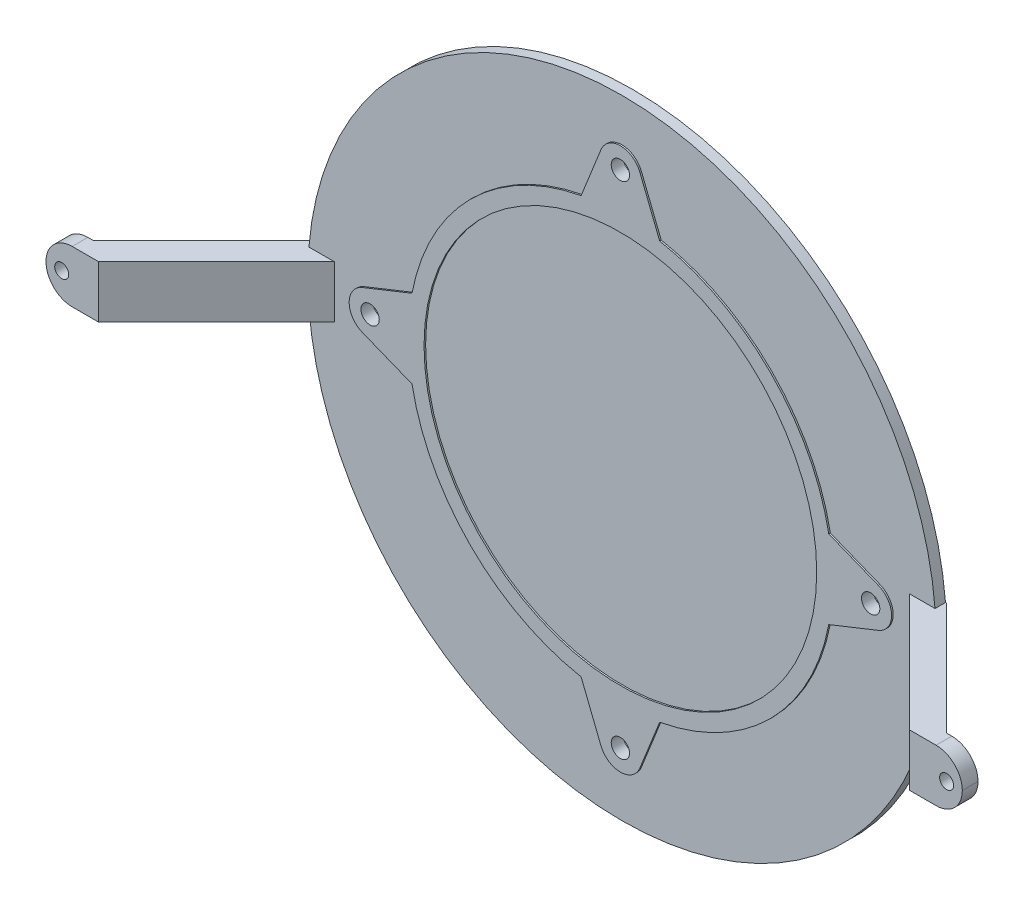
SolidWorks part; units mm, degrees
ref_plane "Front Plane" through (0, 0, 0) normal (0, 0, 1) x (1, 0, 0)
ref_plane "Top Plane" through (0, 0, 0) normal (0, 1, 0) x (1, 0, 0)
ref_plane "Right Plane" through (0, 0, 0) normal (1, 0, 0) x (0, 0, -1)
sketch "Sketch1" plane through (0, 0, 0) normal (0, 0, 1) x (1, 0, 0)
  circle A0 centre (0, 0) radius 60
  dimension "D1" = 120
extrude "Boss-Extrude1" add sketch "Sketch1" along normal blind 2
sketch "Sketch4" plane through (0, 0, 2) normal (0, 0, 1) x (1, 0, 0)
  circle A0 centre (0, 0) radius 37.5
  circle A1 centre (0, 0) radius 40.5
  dimension "D1" = 75
  dimension "D2" = 3
extrude "Boss-Extrude4" add sketch "Sketch4" along normal blind 0.3
sketch "Sketch5" plane through (0, 0, 2) normal (0, 0, 1) x (1, 0, 0)
  line L0 (-7.5, 39.7995) -> (7.5, 39.7995)
  line L1 (7.5, 39.7995) -> (3.715, 49.2823)
  line L2 (-7.5, 39.7995) -> (-3.715, 49.2823)
  line L3 (0, 39.7995) -> (0, 47.7995) construction
  arc A0 (3.715, 49.2823) -> (-3.715, 49.2823) centre (0, 47.7995) ccw
  circle A1 centre (0, 0) radius 40.5 construction
  circle A2 centre (0, 47.7995) radius 1.75
  dimension "D2" = 8
  dimension "D4" = 3.5
  dimension "D1" = 8
  dimension "D3" = 15
extrude "Boss-Extrude5" add sketch "Sketch5" along normal blind 0.3
pattern_circular "CirPattern1" count 4 over 360 about axis through (0, 0, 2) along (0, 0, -1) of "Boss-Extrude5"
sketch "Sketch6" plane through (0, 0, 2) normal (0, 0, 1) x (1, 0, 0)
  circle A1 centre (0, 47.7995) radius 1.75
  circle A2 centre (0, 47.7995) radius 1.75
  circle A3 centre (-47.7995, 0) radius 1.75
  circle A4 centre (-47.7995, 0) radius 1.75
  circle A5 centre (47.7995, 0) radius 1.75
  circle A6 centre (47.7995, 0) radius 1.75
  circle A7 centre (0, -47.7995) radius 1.75
  circle A8 centre (0, -47.7995) radius 1.75
  dimension "D1" = 0
  dimension "D2" = 0
  dimension "D3" = 0
  dimension "D4" = 0
extrude "Cut-Extrude1" cut sketch "Sketch6" against normal through all
sketch "Sketch7" plane through (0, 0, 0) normal (0, 1, 0) x (1, 0, 0)
  line L0 (60, 0) -> (81.5, -21.5)
  line L1 (87.5, -24.5) -> (77.4289, -24.5)
  line L2 (77.4289, -24.5) -> (52.9289, 0)
  line L3 (60, 0) -> (-60, 0) construction
  line L4 (52.9289, 0) -> (60, 0)
  line L6 (81.5, -21.5) -> (87.5, -21.5)
  line L7 (87.5, -21.5) -> (87.5, -24.5)
  point P8 (80.333, -24.4041)
  point P9 (81.3219, -23.5448)
  point P11 (79.0725, -18.8751)
  dimension "D1" = 87.5
  dimension "D2" = 5
  dimension "D3" = 45
  dimension "D4" = 3
  dimension "D5" = 6
extrude "Boss-Extrude6" add sketch "Sketch7" along normal blind 5 and the other way blind 5
sketch "Sketch8" plane through (0, 0, 21.5) normal (0, 0, -1) x (-1, 0, 0)
  line L0 (-87.5, -5) -> (-87.5, 5) construction
  line L1 (-87.5, -5) -> (-81.5, -5) construction
  circle A0 centre (-84.5, 0) radius 1.3376
  point P6 (-88.6269, -5.1735)
  dimension "D1" = 3
  dimension "D2" = 5
extrude "Cut-Extrude2" cut sketch "Sketch8" against normal through all
fillet "Fillet1" radius 5 2 edges at (87.5, -5, 23) (87.5, 5, 23)
mirror "Mirror1" about plane through (0, 0, 0) normal (1, 0, 0) of "Fillet1", "Cut-Extrude2", "Boss-Extrude6"
